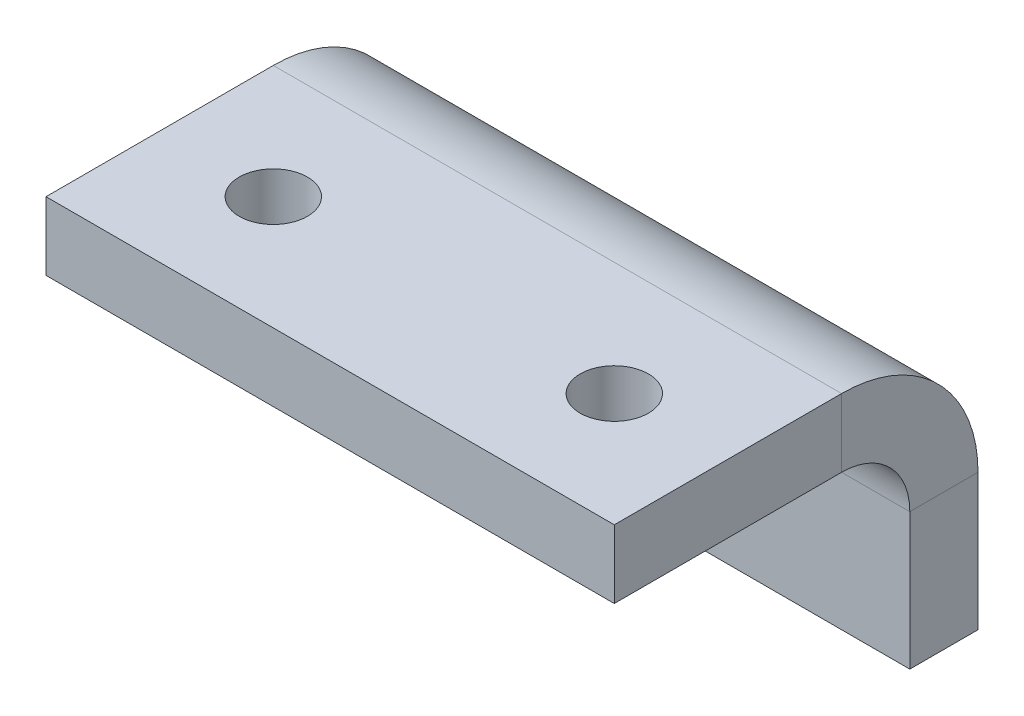
SolidWorks part; units mm, degrees
note: The reader was unsure of these and kept them because the rebuilt part matched: flange length of "邊線-凸緣1".
ref_plane "Front Plane" through (0, 0, 0) normal (0, 0, 1) x (1, 0, 0)
ref_plane "Top Plane" through (0, 0, 0) normal (0, 1, 0) x (1, 0, 0)
ref_plane "Right Plane" through (0, 0, 0) normal (1, 0, 0) x (0, 0, -1)
sketch "Sketch1" plane through (0, 0, 0) normal (0, 1, 0) x (1, 0, 0)
  line L4 (0, 0) -> (0, 10)
  line L5 (0, 0) -> (-25, 0)
  line L6 (0, 10) -> (-25, 10)
  line L7 (-25, 0) -> (-25, 10)
  dimension "D1" = 25
  dimension "D2" = 10
base flange "Base-Flange1" sketch "Sketch1" thickness 3 reverse thickness direction no parameters "D1"=3
sketch "Sketch6" plane through (0, 0, 0) normal (0, 1, 0) x (1, 0, 0)
  line L0 (-25, 5) -> (-20, 5) construction
  line L1 (-25, 10) -> (-25, 0) construction
  line L2 (-20, 5) -> (-5, 5) construction
  line L3 (-5, 5) -> (0, 5) construction
  line L4 (0, 0) -> (0, 10) construction
  dimension "D1" = 15
hole_wizard "Ø3.0 (3) Diameter Hole1" positions "Sketch7" profile "Sketch8" hole size "Ø3.0" standard "ISO" end condition through all
sketch "Sketch7" plane through (0, 0, 0) normal (0, 1, 0) x (1, 0, 0)
  point P0 (-20, 5)
  point P3 (-5, 5)
sketch "Sketch8" plane through (-20, 0, -5) normal (1, 0, 0) x (0, 0, 1)
  line L0 (0, 0) -> (0, 3)
  line L1 (0, 3) -> (1.5, 3)
  line L2 (1.5, 3) -> (1.5, 0)
  line L5 (1.5, 0) -> (0, 0)
  line L11 (0, -6.35) -> (0, 107.95) construction
  dimension "Thru Hole Dia." = 3
  dimension "Thru Hole Depth" = 3
edge flange "邊線-凸緣1" sketch "Sketch11" flange angle 90 flange length 9 flange position bend outside bend radius 3 thickness 3 relief rectangular parameters "D6"=10
sketch "Sketch11" plane through (0, -3, -10) normal (0, 0, -1) x (1, 0, 0)
  line L0 (0, 0) -> (-25, 0) construction
  line L1 (0, 0) -> (-25, 0)
  line L2 (-25, 0) -> (-25, 9)
  line L3 (-25, 9) -> (0, 9)
  line L4 (0, 9) -> (0, 0)
bend "邊線彎折1" bend radius 3 bend angle 90 parameters "D5"=1
sketch "彎折-線1" [suppressed] plane through (0, 0, 0) normal (0, 1, 0) x (1, 0, 0)
sketch "邊界方塊1" [suppressed] plane through (0, 0, 0) normal (0, 1, 0) x (1, 0, 0)
sheet metal parameters "鈑金1" thickness 3 parameters "D1"=3
flat pattern "平板-型式1" [suppressed]
sketch "彎折-線2" plane through (0, 0, 0) normal (0, 1, 0) x (1, 0, 0)
sketch3d "邊界方塊2" [suppressed]
  line L0 (0, 10, 0) -> (20, 10, 0) construction
  line L1 (0, 0, 0) -> (20, 0, 0) construction
  line L2 (0, 10, 0) -> (0, 0, 0) construction
  line L3 (20, 10, 0) -> (20, 0, 0) construction
sheet metal parameters "鈑金2" thickness 3 parameters "D1"=3
flat pattern "平板-型式1"
sketch "彎折-線2" plane through (0, 0, 0) normal (0, 1, 0) x (1, 0, 0)
sketch3d "邊界方塊2" [suppressed]
  line L0 (0, 10, 0) -> (-25, 10, 0) construction
  line L1 (0, 0, 0) -> (-25, 0, 0) construction
  line L2 (0, 10, 0) -> (0, 0, 0) construction
  line L3 (-25, 10, 0) -> (-25, 0, 0) construction
sheet metal parameters "鈑金3" thickness 3 parameters "D1"=3
flat pattern "平板-型式1"
sketch "彎折-線2" plane through (0, 0, 0) normal (0, 1, 0) x (1, 0, 0)
  line L0 (0, 13.3387) -> (-25, 13.3387) construction
  line L1 (0, 13.3387) -> (-25, 13.3387) construction
sketch3d "邊界方塊2" [suppressed]
  line L0 (0, 22.6775, 0) -> (-25, 22.6775, 0) construction
  line L1 (0, 0, 0) -> (-25, 0, 0) construction
  line L2 (0, 22.6775, 0) -> (0, 0, 0) construction
  line L3 (-25, 22.6775, 0) -> (-25, 0, 0) construction
bend of the flat pattern "平板-<邊線彎折1>1"
